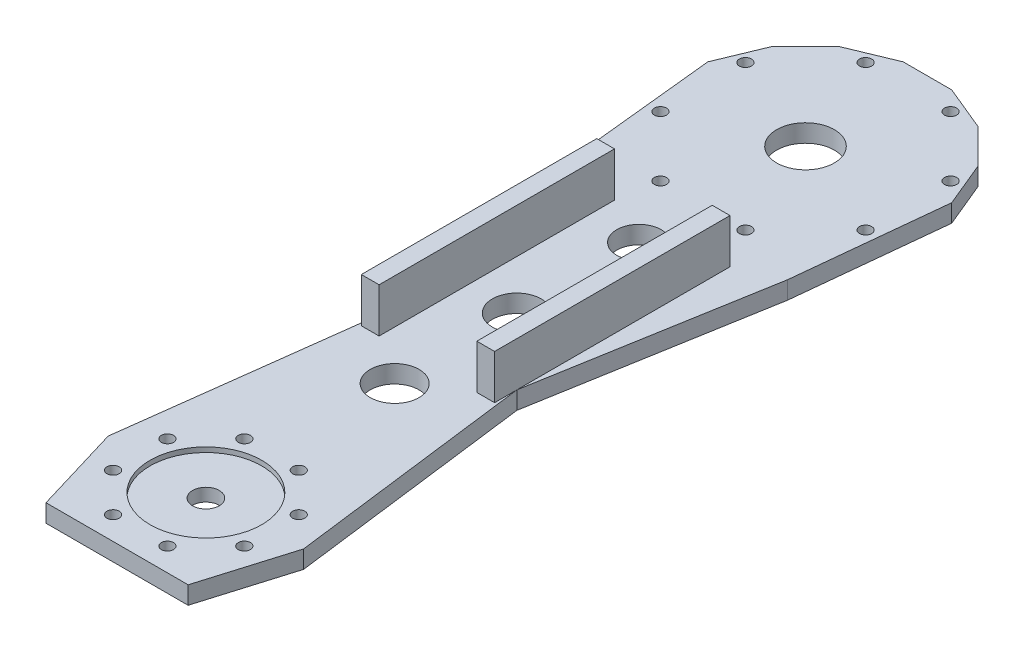
SolidWorks part; units mm, degrees
ref_plane "Front Plane" through (0, 0, 0) normal (0, 0, 1) x (1, 0, 0)
ref_plane "Top Plane" through (0, 0, 0) normal (0, 1, 0) x (1, 0, 0)
ref_plane "Right Plane" through (0, 0, 0) normal (1, 0, 0) x (0, 0, -1)
ref_plane "PL_Thigh_Plate_base" through (0, -44, 0) normal (0, 1, 0) x (1, 0, 0)
sketch "SK_Thigh_Plate" plane through (0, -44, 0) normal (0, 1, 0) x (1, 0, 0)
  line L0 (-32, -40) -> (32, -40)
  line L1 (32, -40) -> (44, 0)
  line L2 (44, 0) -> (30, 110)
  line L3 (30, 110) -> (48, 214)
  line L4 (48, 214) -> (54.924, 280.9251)
  line L5 (54.924, 280.9251) -> (46.5623, 301.1119)
  line L6 (46.5623, 301.1119) -> (31.1119, 316.5623)
  line L7 (31.1119, 316.5623) -> (10.9251, 324.924)
  line L8 (10.9251, 324.924) -> (-10.9251, 324.924)
  line L9 (-10.9251, 324.924) -> (-31.1119, 316.5623)
  line L10 (-31.1119, 316.5623) -> (-46.5623, 301.1119)
  line L11 (-46.5623, 301.1119) -> (-54.924, 280.9251)
  line L12 (-54.924, 280.9251) -> (-48, 214)
  line L13 (-48, 214) -> (-30, 110)
  line L14 (-30, 110) -> (-44, 0)
  line L15 (-44, 0) -> (-32, -40)
  circle A0 centre (29.5641, 12.2459) radius 2.75
  circle A1 centre (12.2459, 29.5641) radius 2.75
  circle A2 centre (-12.2459, 29.5641) radius 2.75
  circle A3 centre (-29.5641, 12.2459) radius 2.75
  circle A4 centre (-29.5641, -12.2459) radius 2.75
  circle A5 centre (-12.2459, -29.5641) radius 2.75
  circle A6 centre (12.2459, -29.5641) radius 2.75
  circle A7 centre (29.5641, -12.2459) radius 2.75
  circle A8 centre (46.194, 289.1342) radius 2.75
  circle A9 centre (19.1342, 316.194) radius 2.75
  circle A10 centre (-19.1342, 316.194) radius 2.75
  circle A11 centre (-46.194, 289.1342) radius 2.75
  circle A12 centre (-46.194, 250.8658) radius 2.75
  circle A13 centre (-19.1342, 223.806) radius 2.75
  circle A14 centre (19.1342, 223.806) radius 2.75
  circle A15 centre (46.194, 250.8658) radius 2.75
  circle A16 centre (0, 0) radius 6
  circle A17 centre (0, 270) radius 13
  circle A18 centre (0, 85) radius 11
  circle A19 centre (0, 140) radius 11
  circle A20 centre (0, 195) radius 10
  dimension "D31_SK_Thigh_Plate" = 5.5
  dimension "D34_SK_Thigh_Plate" = 5.5
  dimension "D37_SK_Thigh_Plate" = 5.5
  dimension "D40_SK_Thigh_Plate" = 5.5
  dimension "D43_SK_Thigh_Plate" = 5.5
  dimension "D46_SK_Thigh_Plate" = 5.5
  dimension "D49_SK_Thigh_Plate" = 5.5
  dimension "D52_SK_Thigh_Plate" = 5.5
  dimension "D55_SK_Thigh_Plate" = 5.5
  dimension "D58_SK_Thigh_Plate" = 5.5
  dimension "D61_SK_Thigh_Plate" = 5.5
  dimension "D64_SK_Thigh_Plate" = 5.5
  dimension "D67_SK_Thigh_Plate" = 5.5
  dimension "D70_SK_Thigh_Plate" = 5.5
  dimension "D73_SK_Thigh_Plate" = 5.5
  dimension "D76_SK_Thigh_Plate" = 5.5
  dimension "D79_SK_Thigh_Plate" = 12
  dimension "D80_SK_Thigh_Plate" = 26
  dimension "D82_SK_Thigh_Plate" = 22
  dimension "D84_SK_Thigh_Plate" = 22
  dimension "D86_SK_Thigh_Plate" = 20
  dimension "P1" = 32
  dimension "P2" = 40
  dimension "P3" = 32
  dimension "P4" = 40
  dimension "P5" = 44
  dimension "P6" = 30
  dimension "P7" = 110
  dimension "P8" = 48
  dimension "P9" = 214
  dimension "P10" = 54.924
  dimension "P11" = 280.9251
  dimension "P12" = 46.5623
  dimension "P13" = 301.1119
  dimension "P14" = 31.1119
  dimension "P15" = 316.5623
  dimension "P16" = 10.9251
  dimension "P17" = 324.924
  dimension "P18" = 10.9251
  dimension "P19" = 324.924
  dimension "P20" = 31.1119
  dimension "P21" = 316.5623
  dimension "P22" = 46.5623
  dimension "P23" = 301.1119
  dimension "P24" = 54.924
  dimension "P25" = 280.9251
  dimension "P26" = 48
  dimension "P27" = 214
  dimension "P28" = 30
  dimension "P29" = 110
  dimension "P30" = 44
  dimension "P32" = 29.5641
  dimension "P33" = 12.2459
  dimension "P35" = 12.2459
  dimension "P36" = 29.5641
  dimension "P38" = 12.2459
  dimension "P39" = 29.5641
  dimension "P41" = 29.5641
  dimension "P42" = 12.2459
  dimension "P44" = 29.5641
  dimension "P45" = 12.2459
  dimension "P47" = 12.2459
  dimension "P48" = 29.5641
  dimension "P50" = 12.2459
  dimension "P51" = 29.5641
  dimension "P53" = 29.5641
  dimension "P54" = 12.2459
  dimension "P56" = 46.194
  dimension "P57" = 289.1342
  dimension "P59" = 19.1342
  dimension "P60" = 316.194
  dimension "P62" = 19.1342
  dimension "P63" = 316.194
  dimension "P65" = 46.194
  dimension "P66" = 289.1342
  dimension "P68" = 46.194
  dimension "P69" = 250.8658
  dimension "P71" = 19.1342
  dimension "P72" = 223.806
  dimension "P74" = 19.1342
  dimension "P75" = 223.806
  dimension "P77" = 46.194
  dimension "P78" = 250.8658
  dimension "P81" = 270
  dimension "P83" = 85
  dimension "P85" = 140
  dimension "P87" = 195
extrude "Thigh_Plate" add sketch "SK_Thigh_Plate" along normal blind 8
ref_plane "PL_Pitch_Pilot_Recess_base" through (0, -36, 0) normal (0, 1, 0) x (1, 0, 0)
sketch "SK_Pitch_Pilot_Recess" plane through (0, -36, 0) normal (0, 1, 0) x (1, 0, 0)
  circle A0 centre (0, 0) radius 25.15
  dimension "D1_SK_Pitch_Pilot_Recess" = 50.3
extrude "Pitch_Pilot_Recess" cut sketch "SK_Pitch_Pilot_Recess" against normal blind 2.2
ref_plane "PL_Front_Flange_base" through (22, 0, 0) normal (1, 0, 0) x (0, 0, -1)
sketch "SK_Front_Flange" plane through (22, 0, 0) normal (1, 0, 0) x (0, 0, -1)
  line L0 (206, -16) -> (206, -36)
  line L1 (206, -36) -> (100, -36)
  line L2 (100, -36) -> (100, -16)
  line L3 (100, -16) -> (206, -16)
  dimension "P1" = 206
  dimension "P2" = 16
  dimension "P3" = 206
  dimension "P4" = 36
  dimension "P5" = 100
  dimension "P6" = 36
  dimension "P7" = 100
  dimension "P8" = 16
extrude "Front_Flange" add sketch "SK_Front_Flange" along normal blind 8
ref_plane "PL_Back_Flange_base" through (-30, 0, 0) normal (1, 0, 0) x (0, 0, -1)
sketch "SK_Back_Flange" plane through (-30, 0, 0) normal (1, 0, 0) x (0, 0, -1)
  line L0 (206, -16) -> (206, -36)
  line L1 (206, -36) -> (100, -36)
  line L2 (100, -36) -> (100, -16)
  line L3 (100, -16) -> (206, -16)
  dimension "P1" = 206
  dimension "P2" = 16
  dimension "P3" = 206
  dimension "P4" = 36
  dimension "P5" = 100
  dimension "P6" = 36
  dimension "P7" = 100
  dimension "P8" = 16
extrude "Back_Flange" add sketch "SK_Back_Flange" along normal blind 8
ref_axis "AX_PitchY" through (0, -14.6, 0) along (0, -1, 0)
ref_plane "PL_PitchRef" through (0, 0, 0) normal (-0.6428, 0, 0.766) x (0, -1, 0)
equation "\"Thigh_length\" = 270"
equation "\"Thigh_plate_t\" = 8"
equation "\"Flange_end_z\" = -206"
